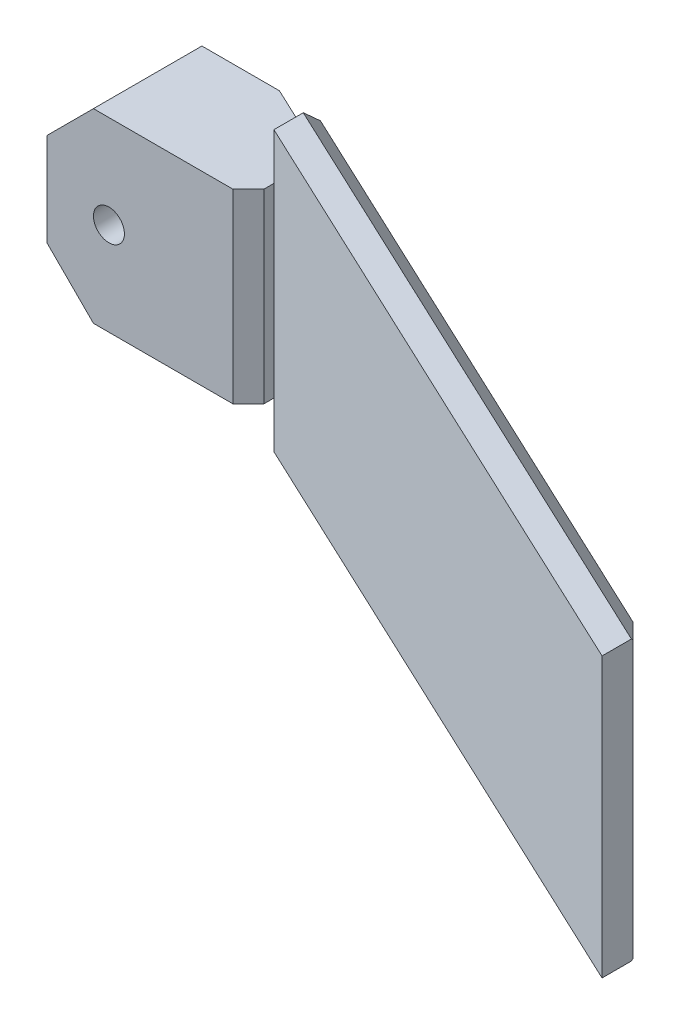
SolidWorks part; units mm, degrees
ref_plane "Alzado" through (0, 0, 0) normal (0, 0, 1) x (1, 0, 0)
ref_plane "Planta" through (0, 0, 0) normal (0, 1, 0) x (1, 0, 0)
ref_plane "Vista lateral" through (0, 0, 0) normal (1, 0, 0) x (0, 0, -1)
sketch "Croquis1" plane through (0, 0, 0) normal (0, 1, 0) x (1, 0, 0)
  line L0 (4, -1.5) -> (49, -22.6765)
  line L1 (-4, -1.5) -> (4, -1.5)
  line L2 (-4, -1.5) -> (-4, 1.5)
  line L3 (-4, 1.5) -> (4, 1.5)
  line L5 (-4, -1.5) -> (4, 1.5) construction
  line L6 (-4, 1.5) -> (4, -1.5) construction
  line L7 (4, 1.5) -> (49, -19.6765)
  line L8 (49, -19.6765) -> (49, -22.6765)
  line L9 (49, -22.6765) -> (4, -22.6765) construction
  line L10 (4, -1.5) -> (4, -22.6765) construction
  point P0 (0, 0)
  point P6 (4.1457, -17.5)
  dimension "D1" = 3
  dimension "D2" = 3
  dimension "D3" = 8
  dimension "D5" = 45
  dimension "D6" = 25.201
extrude "Saliente-Extruir1" add sketch "Croquis1" along normal blind 18
sketch "Croquis2" plane through (0, 0, -1.5) normal (0, 0, -1) x (-1, 0, 0)
  line L0 (4, 9) -> (-5.3709, 9) construction
  line L1 (4, 18) -> (4, 0) construction
  line L2 (0, 18) -> (0, 0) construction
  line L3 (-4, 18) -> (4, 18) construction
  circle A0 centre (0, 9) radius 2.5
  dimension "D1" = 5
extrude "Cortar-Extruir1" cut sketch "Croquis2" against normal blind 2.5
sketch "Croquis3" plane through (0, 0, -1.5) normal (0, 0, -1) x (-1, 0, 0)
  line L1 (4, 18) -> (-9, 18)
  line L2 (4, 18) -> (4, 15)
  line L3 (4, 15) -> (-9, 15)
  line L4 (-9, 18) -> (-9, 15)
  line L5 (4, 0) -> (-9, 0)
  line L6 (4, 0) -> (4, 3)
  line L7 (4, 3) -> (-9, 3)
  line L8 (-9, 0) -> (-9, 3)
  dimension "D1" = 3
  dimension "D2" = 3
  dimension "D3" = 13
extrude "Cortar-Extruir2" cut sketch "Croquis3" against normal through all
chamfer "Chaflán1" distance 1 angle 45 2 edges at (29, 0, 10.2647) (29, 18, 10.2647)
chamfer "Chaflán2" distance 1 angle 45 1 edges at (49, 9, 19.6765) first distance on face at (49, 9, 21.0449)
sketch "Croquis4" plane through (0, 0, 1.5) normal (0, 0, 1) x (1, 0, 0)
  line L0 (9, 18) -> (9, 15) construction
  line L1 (9, 15) -> (-4, 15)
  line L2 (9, 15) -> (9, 3)
  line L3 (9, 3) -> (-4, 3)
  line L4 (-4, 15) -> (-4, 3)
  point P6 (0, 0)
extrude "Saliente-Extruir2" add sketch "Croquis4" along normal blind 4
sketch "Croquis5" plane through (0, 0, 1) normal (0, 0, -1) x (-1, 0, 0)
  circle A0 centre (0, 9) radius 1
  dimension "D1" = 2
extrude "Cortar-Extruir3" cut sketch "Croquis5" against normal through all
chamfer "Chaflán3" distance 3 angle 45 2 edges at (-4, 15, 2) (-4, 3, 2)
chamfer "Chaflán4" distance 1 angle 45 1 edges at (9, 9, 5.5)
